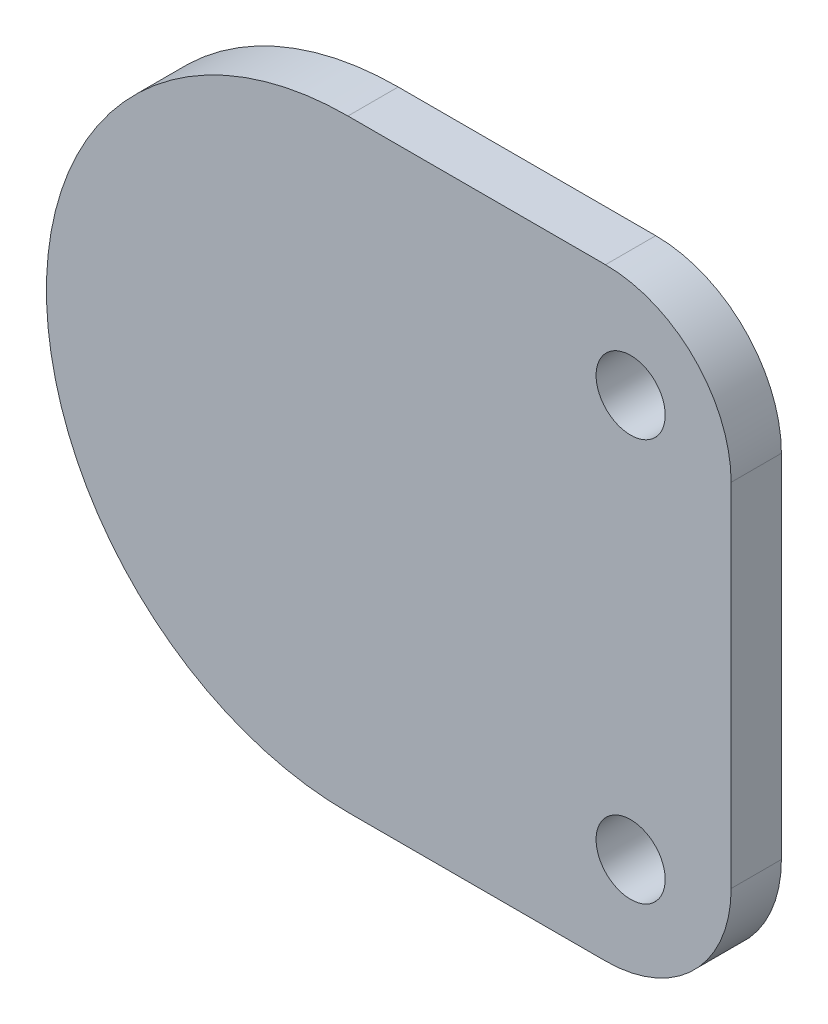
SolidWorks part; units mm, degrees
ref_plane "Front Plane" through (0, 0, 0) normal (0, 0, 1) x (1, 0, 0)
ref_plane "Top Plane" through (0, 0, 0) normal (0, 1, 0) x (1, 0, 0)
ref_plane "Right Plane" through (0, 0, 0) normal (1, 0, 0) x (0, 0, -1)
ref_axis "X-Axis" through (88.99, 0, 0) along (-1, 0, 0)
ref_axis "Y-Axis" through (0, 0, -88.99) along (0, 0, 1)
ref_axis "Z-Axis" through (0, -55, 0) along (0, 1, 0)
sketch "Sketch1" plane through (0, 0, 0) normal (0, 0, 1) x (1, 0, 0)
  line L0 (0, -55) -> (0, 55) construction
  line L1 (88.99, 0) -> (-88.99, 0) construction
  line L6 (0, -24) -> (20.5, -24)
  line L7 (30.5, -14) -> (30.5, 14)
  line L8 (20.5, 24) -> (0, 24)
  circle A2 centre (22.5, -16) radius 2.75
  arc A6 (0, 24) -> (0, -24) centre (0, 0) ccw
  arc A7 (20.5, -24) -> (30.5, -14) centre (20.5, -14) ccw
  arc A8 (30.5, 14) -> (20.5, 24) centre (20.5, 14) ccw
  circle A9 centre (22.5, 16) radius 2.75
  point P5 (0, 0)
  point P18 (0, 0)
  dimension "D1" = 5.5
  dimension "D2" = 5.5
  dimension "D8" = 24
  dimension "D11" = 10
  dimension "D3" = 22.5
  dimension "D4" = 16
  dimension "D5" = 16
  dimension "D6" = 22.5
  dimension "D7" = 30.5
  dimension "D9" = 10
  dimension "D10" = 24
extrude "Boss-Extrude1" add sketch "Sketch1" along normal blind 4
sketch "Sketch2" plane through (0, 0, 0) normal (0, 0, -1) x (-1, 0, 0)
  circle A0 centre (0, 0) radius 16
  circle A1 centre (0, 0) radius 14
  dimension "D1" = 32
  dimension "D2" = 2
extrude "Boss-Extrude2" add sketch "Sketch2" along normal blind 6
